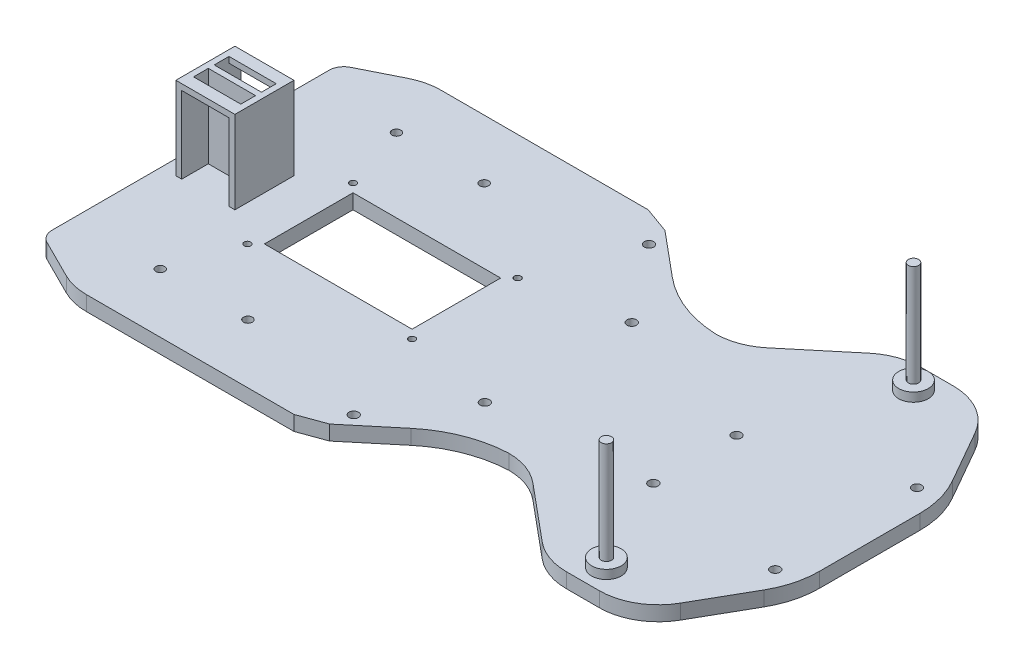
SolidWorks part; units mm, degrees
ref_plane "Front Plane" through (0, 0, 0) normal (0, 0, 1) x (1, 0, 0)
ref_plane "Top Plane" through (0, 0, 0) normal (0, 1, 0) x (1, 0, 0)
ref_plane "Right Plane" through (0, 0, 0) normal (1, 0, 0) x (0, 0, -1)
sketch "Sketch1" plane through (0, 0, 0) normal (0, 1, 0) x (1, 0, 0)
  line L0 (40, 60) -> (70, 60)
  line L1 (70, 60) -> (90, 25)
  line L2 (90, 25) -> (90, -25)
  line L3 (90, -25) -> (70, -60)
  line L4 (70, -60) -> (40, -60)
  line L5 (40, 60) -> (10, 35)
  line L6 (10, 35) -> (-10, 35)
  line L7 (-10, 35) -> (-40, 60)
  line L8 (-40, 60) -> (-120, 60)
  line L9 (-120, 60) -> (-140, 50)
  line L10 (-140, 50) -> (-140, -50)
  line L11 (-140, -50) -> (-120, -60)
  line L12 (-120, -60) -> (-40, -60)
  line L13 (-40, -60) -> (-10, -35)
  line L14 (-10, -35) -> (10, -35)
  line L15 (10, -35) -> (40, -60)
  point P31 (90, 0)
  point P33 (0, 35)
  point P35 (-140, 0)
  dimension "D1" = 120
  dimension "D2" = 70
  dimension "D3" = 20
  dimension "D4" = 30
  dimension "D5" = 20
  dimension "D6" = 100
  dimension "D7" = 100
  dimension "D8" = 20
  dimension "D9" = 30
  dimension "D10" = 50
extrude "Boss-Extrude1" add sketch "Sketch1" along normal blind 5
chamfer "Chamfer1" distance 5 angle 20 2 edges at (-40, 2.5, -60) (-40, 2.5, 60) first distance on face at (-25, 2.5, -47.5) first distance on face at (-80, 2.5, 60)
fillet "Fillet4" radius 20 4 edges at (40, 2.5, -60) (40, 2.5, 60) (70, 2.5, -60) (70, 2.5, 60)
sketch "Sketch3" plane through (0, 5, 0) normal (0, 1, 0) x (1, 0, 0)
  line L0 (58.3935, 60) -> (47.241, 60) construction
  line L2 (47.241, -60) -> (58.3935, -60) construction
  circle A0 centre (52.8173, 52) radius 1.75
  circle A1 centre (52.8173, -52) radius 1.75
  point P5 (52.8173, 60)
  dimension "D3" = 3.5
  dimension "D1" = 8
  dimension "D2" = 8
fillet "Fillet5" radius 30 2 edges at (90, 2.5, 25) (90, 2.5, -25)
fillet "Fillet6" radius 20 2 edges at (10, 2.5, -35) (10, 2.5, 35)
fillet "Fillet7" radius 40 2 edges at (-10, 2.5, -35) (-10, 2.5, 35)
fillet "Fillet8" radius 20 2 edges at (-120, 2.5, 60) (-120, 2.5, -60)
fillet "Fillet9" radius 5 2 edges at (-140, 2.5, 50) (-140, 2.5, -50)
sketch "Sketch7" plane through (0, 5, 0) normal (0, 1, 0) x (1, 0, 0)
  line L0 (-45.0471, 60) -> (-115.2786, 60) construction
  circle A0 centre (-110.2786, 40) radius 1.5
  circle A1 centre (-80.5786, 40) radius 1.5
  dimension "D1" = 5
  dimension "D2" = 3
  dimension "D3" = 29.7
  dimension "D4" = 20
extrude "Cut-Extrude3" cut sketch "Sketch7" against normal up to next
mirror "Mirror1" about plane through (0, 0, 0) normal (0, 0, 1) of "Cut-Extrude3"
extrude "Boss-Extrude2" add sketch "Sketch3" along normal blind 37.5
sketch "Sketch8" plane through (0, 5, 0) normal (0, 1, 0) x (1, 0, 0)
  circle A0 centre (52.8173, 52) radius 5
  circle A1 centre (52.8173, -52) radius 5
  dimension "D1" = 10
extrude "Boss-Extrude3" add sketch "Sketch8" along normal blind 3
sketch "Sketch9" plane through (0, 5, 0) normal (0, 1, 0) x (1, 0, 0)
  line L1 (-135, 10) -> (-115, 10)
  line L2 (-135, 10) -> (-135, -10)
  line L4 (-115, 10) -> (-115, -10)
  line L5 (-45.0471, 60) -> (-115.2786, 60) construction
  line L8 (-135, -10) -> (-115, -10)
  line L12 (-140, 46.9098) -> (-140, -46.9098) construction
  dimension "D1" = 50
  dimension "D2" = 5
  dimension "D3" = 20
  dimension "D4" = 20
extrude "Boss-Extrude4" add sketch "Sketch9" along normal blind 28
sketch "Sketch12" plane through (0, 33, 0) normal (0, 1, 0) x (1, 0, 0)
  line L0 (-135, -10) -> (-115, -10) construction
  line L1 (-133, -1) -> (-117, -1)
  line L2 (-133, -1) -> (-133, -6)
  line L3 (-133, -6) -> (-117, -6)
  line L4 (-117, -1) -> (-117, -6)
  line L5 (-133, 6) -> (-117, 6)
  line L6 (-133, 6) -> (-133, 1)
  line L7 (-133, 1) -> (-117, 1)
  line L8 (-117, 6) -> (-117, 1)
  line L9 (-115, 10) -> (-135, 10) construction
  point P8 (-125, -6)
  point P11 (-125, -10)
  point P12 (-125, 1)
  point P13 (-125, -1)
  dimension "D1" = 4
  dimension "D2" = 5
  dimension "D3" = 16
  dimension "D4" = 4
extrude "Cut-Extrude5" cut sketch "Sketch12" against normal up to surface (28 mm away) up to face at (52.8173, 5, 57)
sketch "Sketch13" plane through (0, 0, -10) normal (0, 0, -1) x (-1, 0, 0)
  line L0 (115, 5) -> (135, 5) construction
  line L1 (117, 5) -> (133, 5)
  line L2 (117, 5) -> (117, 31)
  line L3 (117, 31) -> (133, 31)
  line L4 (133, 5) -> (133, 31)
  line L5 (115, 33) -> (135, 33) construction
  point P8 (125, 33)
  point P9 (125, 31)
  dimension "D1" = 2
  dimension "D2" = 16
extrude "Cut-Extrude7" cut sketch "Sketch13" against normal up to next
mirror "Mirror2" about plane through (0, 0, 0) normal (0, 0, 1) of "Cut-Extrude7"
sketch "Sketch14" plane through (0, 5, 0) normal (0, 1, 0) x (1, 0, 0)
  line L0 (-140, 46.9098) -> (-140, -46.9098) construction
  line L1 (-105, 20) -> (-45, 20) construction
  line L2 (-105, 20) -> (-105, -20) construction
  line L3 (-105, -20) -> (-45, -20) construction
  line L4 (-45, 20) -> (-45, -20) construction
  line L5 (-115, -10) -> (-115, 10) construction
  point P4 (-105, 0)
  point P7 (-140, 0)
  dimension "D1" = 40
  dimension "D2" = 60
  dimension "D3" = 10
sketch "Sketch15" plane through (0, 5, 0) normal (0, 1, 0) x (1, 0, 0)
  line L0 (-105, 20) -> (-105, -20) construction
  line L1 (-105, 20) -> (-45, 20) construction
  line L2 (-45, 20) -> (-45, -20) construction
  line L3 (-105, -20) -> (-45, -20) construction
  circle A0 centre (-102.875, 17.875) radius 1.125
  circle A1 centre (-102.875, -17.875) radius 1.125
  circle A2 centre (-47.125, -17.875) radius 1.125
  circle A3 centre (-47.125, 17.875) radius 1.125
  dimension "D2" = 2.25
  dimension "D1" = 2.125
  dimension "D3" = 2.125
  dimension "D4" = 2.125
  dimension "D5" = 2.125
extrude "Cut-Extrude8" cut sketch "Sketch15" against normal up to next
sketch "Sketch16" plane through (0, 5, 0) normal (0, 1, 0) x (1, 0, 0)
  line L0 (-105, 20) -> (-105, -20) construction
  line L1 (-100, 15) -> (-50, 15)
  line L2 (-100, 15) -> (-100, -15)
  line L3 (-100, -15) -> (-50, -15)
  line L4 (-50, 15) -> (-50, -15)
  line L5 (-105, 20) -> (-45, 20) construction
  point P6 (-105, 0)
  point P7 (-100, 0)
  point P10 (-75, 20)
  point P11 (-75, 15)
  dimension "D1" = 30
  dimension "D2" = 50
extrude "Cut-Extrude10" cut sketch "Sketch16" against normal up to next
sketch "Sketch17" plane through (0, 5, 0) normal (0, 1, 0) x (1, 0, 0)
  line L1 (-30, 26.7) -> (38.6, 26.7) construction
  line L2 (-30, 26.7) -> (-30, -26.7) construction
  line L3 (-30, -26.7) -> (38.6, -26.7) construction
  line L4 (38.6, 26.7) -> (38.6, -26.7) construction
  line L7 (-45, 20) -> (-45, -20) construction
  circle A0 centre (-14.75, 24.16) radius 1.6
  circle A1 centre (-16.2, -24.15) radius 1.6
  circle A2 centre (36.06, -19.34) radius 1.6
  circle A3 centre (36.06, 8.83) radius 1.6
  point P7 (-30, 0)
  dimension "D6" = 1.45
  dimension "D7" = 3.2
  dimension "D1" = 68.6
  dimension "D2" = 53.4
  dimension "D3" = 2.54
  dimension "D4" = 15.25
  dimension "D5" = 48.31
  dimension "D8" = 7.36
  dimension "D9" = 2.54
  dimension "D10" = 28.17
  dimension "D11" = 15
extrude "Cut-Extrude11" cut sketch "Sketch17" against normal up to next
sketch "Sketch18" plane through (0, 5, 0) normal (0, 1, 0) x (1, 0, 0)
  line L0 (90, -17.0331) -> (90, 17.0331) construction
  line L2 (82, 24) -> (82, -24) construction
  circle A0 centre (82, 24) radius 1.6
  circle A1 centre (82, -24) radius 1.6
  point P4 (82, 0)
  point P7 (90, 0)
  point P8 (0, 0)
  dimension "D3" = 3.2
  dimension "D1" = 48
  dimension "D2" = 8
extrude "Cut-Extrude12" cut sketch "Sketch18" against normal up to next
sketch "Sketch19" plane through (0, 5, 0) normal (0, 1, 0) x (1, 0, 0)
  line L0 (-115.2786, -60) -> (-45, -60) construction
  line L1 (-45.0471, 60) -> (-115.2786, 60) construction
  circle A0 centre (-34.75, -50) radius 1.6
  circle A1 centre (-34.75, 50) radius 1.6
  circle A2 centre (-14.75, 24.16) radius 1.6 construction
  point P4 (0, 0)
  point P7 (0, 0)
  point P9 (0, -30)
  point P10 (0, -30.0737)
  point P11 (-27.772, -31.2959)
  point P12 (-29.096, -32.0088)
  point P19 (-34.75, -45)
  dimension "D3" = 20
  dimension "D4" = 3.2
  dimension "D1" = 10
  dimension "D2" = 10
extrude "Cut-Extrude13" cut sketch "Sketch19" against normal up to next
